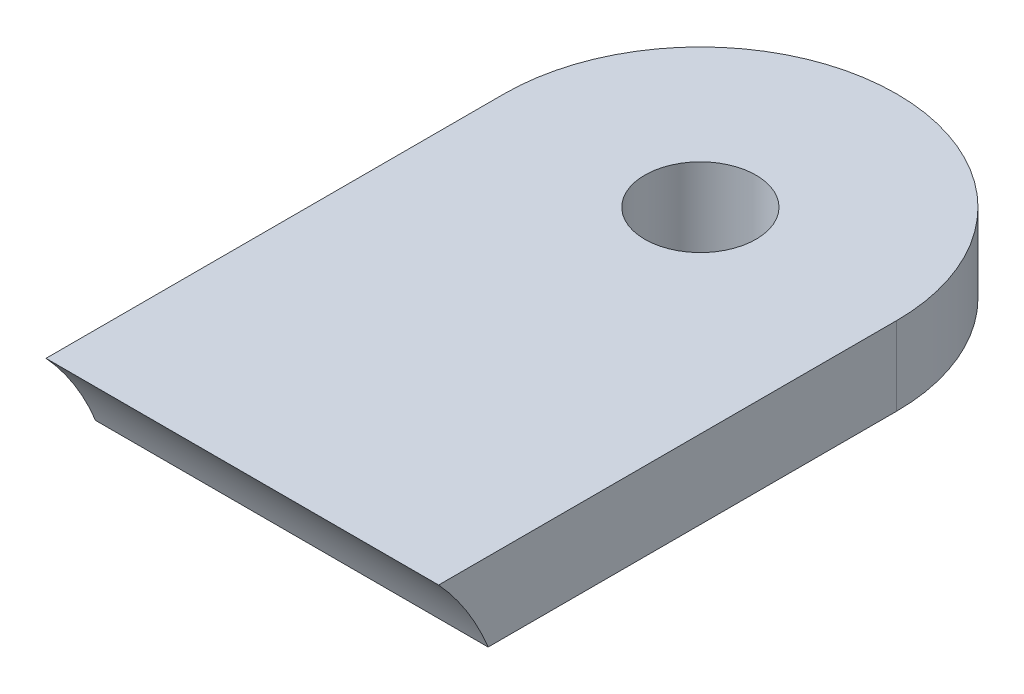
SolidWorks part; units mm, degrees
ref_plane "Front Plane" through (0, 0, 0) normal (0, 0, 1) x (1, 0, 0)
ref_plane "Top Plane" through (0, 0, 0) normal (0, 1, 0) x (1, 0, 0)
ref_plane "Right Plane" through (0, 0, 0) normal (1, 0, 0) x (0, 0, -1)
sketch "Sketch1" plane through (0, 0, 0) normal (0, 1, 0) x (1, 0, 0)
  line L0 (-15, 50) -> (-15, 35) construction
  line L1 (0, 0) -> (-30, 0)
  line L2 (0, 0) -> (0, 50)
  line L3 (0, 50) -> (-30, 50)
  line L4 (-30, 0) -> (-30, 50)
  circle A0 centre (-15, 35) radius 4.25
  dimension "D3" = 8.5
  dimension "D4" = 35
  dimension "D2" = 15
  dimension "D1" = 30
extrude "Boss-Extrude1" add sketch "Sketch1" along normal blind 6
fillet "Fillet1" radius 15 2 edges at (-30, 3, -50) (0, 3, -50)
sketch "Sketch2" plane through (-30, 0, 0) normal (-1, 0, 0) x (0, 0, 1)
  line L0 (-35, 0) -> (0, 0) construction
  circle A0 centre (14.7564, -7.5) radius 20
  dimension "D1" = 40
  dimension "D2" = 7.5
extrude "Cut-Extrude1" cut sketch "Sketch2" against normal through all
